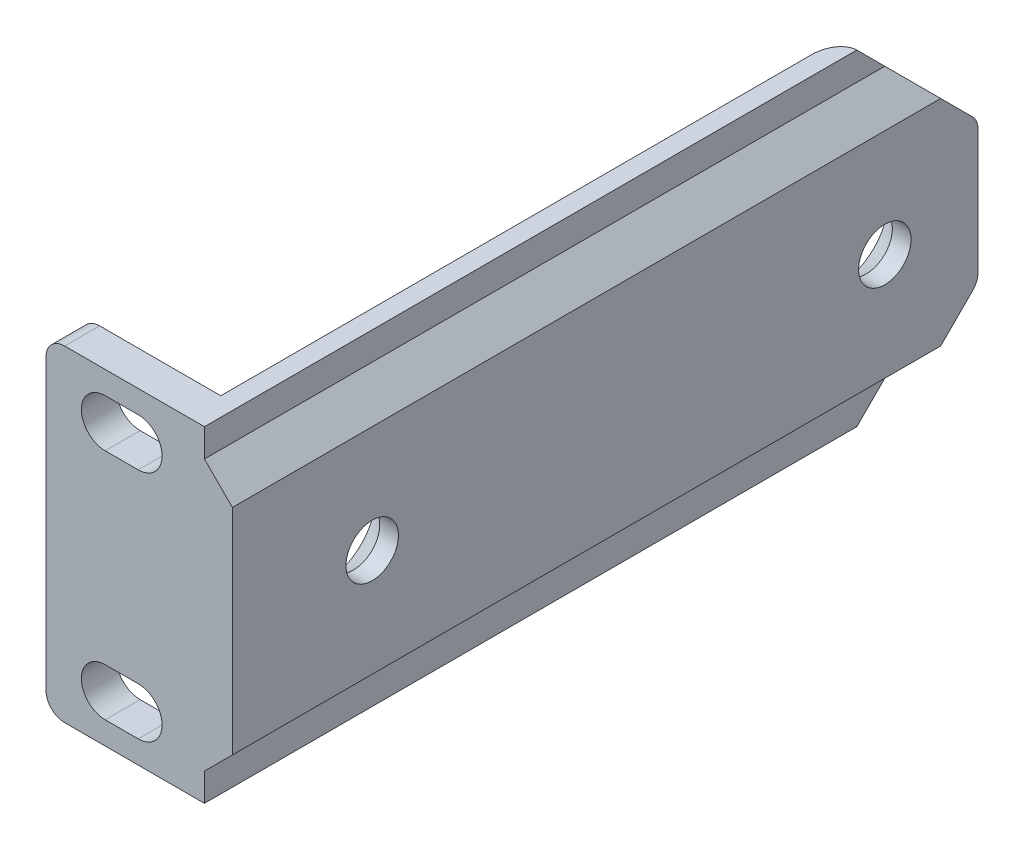
SolidWorks part; units mm, degrees
ref_plane "Plane XZ" through (0, 0, 0) normal (0, 0, 1) x (1, 0, 0)
ref_plane "Plane XY" through (0, 0, 0) normal (0, 1, 0) x (1, 0, 0)
ref_plane "Plane YZ" through (0, 0, 0) normal (1, 0, 0) x (0, 0, -1)
sketch "Sketch1" plane through (0, 0, 0) normal (0, 1, 0) x (1, 0, 0)
  line L0 (0, 0) -> (0, 101.6)
  line L1 (0, 101.6) -> (-6.35, 101.6)
  line L2 (-6.35, 101.6) -> (-6.35, 4.7625)
  line L3 (-6.35, 4.7625) -> (-25.4, 4.7625)
  line L4 (-25.4, 4.7625) -> (-25.4, 0)
  line L5 (-25.4, 0) -> (0, 0)
  dimension "D1" = 4.7625
  dimension "D2" = 6.35
  dimension "D3" = 101.6
  dimension "D4" = 25.4
extrude "Boss-Extrude1" add sketch "Sketch1" along normal mid plane 44.45
sketch "Sketch2" plane through (0, 0, 0) normal (0, 0, 1) x (1, 0, 0)
  line L1 (0, 22.225) -> (-3.81, 22.225)
  line L2 (0, 22.225) -> (0, 18.415)
  line L3 (0, 18.415) -> (-3.81, 18.415)
  line L4 (-3.81, 22.225) -> (-3.81, 18.415)
  line L5 (0, -22.225) -> (-3.81, -22.225)
  line L6 (0, -22.225) -> (0, -18.415)
  line L7 (0, -18.415) -> (-3.81, -18.415)
  line L8 (-3.81, -22.225) -> (-3.81, -18.415)
  dimension "D1" = 3.81
  dimension "D2" = 3.81
extrude "Cut-Extrude1" cut sketch "Sketch2" against normal through all
sketch "Sketch3" plane through (0, 0, 0) normal (0, 0, 1) x (1, 0, 0)
  line L0 (0, 0) -> (-25.4, 0) construction
  line L1 (0, 18.415) -> (0, -18.415) construction
  line L2 (-25.4, 22.225) -> (-25.4, -22.225) construction
  line L3 (-12.8333, -15.875) -> (-17.3291, -15.875) construction
  line L4 (-12.8334, -19.1262) -> (-17.3291, -19.1262)
  line L5 (-12.8334, -12.6238) -> (-17.3291, -12.6238)
  line L6 (-17.3291, -15.875) -> (-20.5803, -15.875) construction
  line L7 (-12.8333, -15.875) -> (-9.5821, -15.875) construction
  line L8 (-12.8333, 15.875) -> (-17.3291, 15.875) construction
  line L9 (-12.8334, 19.1262) -> (-17.3291, 19.1262)
  line L10 (-12.8334, 12.6238) -> (-17.3291, 12.6238)
  arc A0 (-12.8334, -19.1262) -> (-12.8334, -12.6238) centre (-12.8333, -15.875) ccw
  arc A1 (-17.3291, -12.6238) -> (-17.3291, -19.1262) centre (-17.3291, -15.875) ccw
  arc A2 (-12.8334, 19.1262) -> (-12.8334, 12.6238) centre (-12.8333, 15.875) cw
  arc A3 (-17.3291, 12.6238) -> (-17.3291, 19.1262) centre (-17.3291, 15.875) cw
  point P8 (-15.0812, -15.875)
  point P19 (-15.0812, 15.875)
  dimension "D2" = 6.5024
  dimension "D1" = 10.9982
  dimension "D3" = 15.0812
  dimension "D4" = 15.875
extrude "Cut-Extrude2" cut sketch "Sketch3" against normal through all
fillet "Fillet1" radius 2.54 2 edges at (-25.4, 22.225, -2.3813) (-25.4, -22.225, -2.3813)
hole_wizard "CSK for 1/4 Flat Head Machine Screw1" positions "Sketch4" profile "Sketch5" countersink size "1/4" standard "ANSI Inch" end condition through all
sketch "Sketch4" plane through (-6.35, 0, 0) normal (-1, 0, 0) x (0, 0, 1)
  line L0 (-88.9, 0) -> (-19.05, 0)
  line L1 (-19.05, 0) -> (0, 0)
  point P0 (-19.05, 0)
  point P2 (-88.9, 0)
  dimension "D1" = 19.05
  dimension "D2" = 88.9
sketch "Sketch5" plane through (-6.35, 0, -19.05) normal (0, 1, 0) x (0, 0, 1)
  line L0 (0, 0) -> (0, 6.35)
  line L1 (0, 6.35) -> (3.5712, 6.35)
  line L2 (3.5712, 6.35) -> (3.5712, 3.8069)
  line L3 (3.5712, 3.8069) -> (6.8805, 0)
  line L5 (6.8805, 0) -> (0, 0)
  line L6 (-3.5712, 3.8069) -> (-6.8805, 0) construction
  line L11 (0, -6.35) -> (0, 107.95) construction
  dimension "Thru Hole Dia." = 7.1425
  dimension "Thru Hole Depth" = 6.35
  dimension "Near C'Sink Dia." = 13.761
  dimension "Near C'Sink Angle" = 82
sketch "Sketch6" plane through (-6.35, 0, 0) normal (-1, 0, 0) x (0, 0, 1)
  line L0 (-88.9, -22.225) -> (-101.6, -22.225)
  line L1 (-101.6, -22.225) -> (-4.7625, -22.225) construction
  line L2 (-101.6, -22.225) -> (-101.6, -9.525)
  line L3 (-101.6, 22.225) -> (-101.6, -22.225) construction
  line L4 (-101.6, -9.525) -> (-88.9, -22.225)
  line L5 (-101.6, 0) -> (0, 0) construction
  line L6 (-101.6, 22.225) -> (-101.6, 9.525)
  line L7 (-88.9, 22.225) -> (-101.6, 22.225)
  line L8 (-101.6, 9.525) -> (-88.9, 22.225)
  dimension "D1" = 12.7
extrude "Cut-Extrude3" cut sketch "Sketch6" against normal through all
fillet "Fillet2" radius 2.54 5 edges at (-6.35, -15.875, -95.25) (-6.35, 0, -101.6) (-6.35, 15.875, -95.25) (-3.175, 9.525, -101.6) (-3.175, -9.525, -101.6)
chamfer "Chamfer1" distance 3.81 angle 45 2 edges at (0, 18.415, -46.355) (0, -18.415, -46.355)
